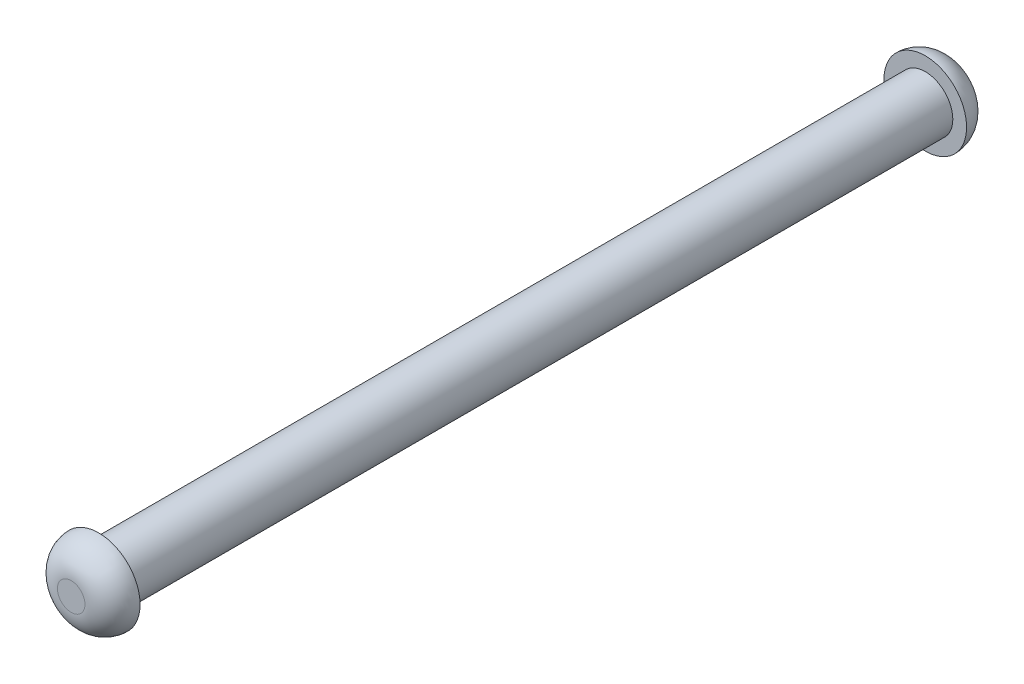
SolidWorks part; units mm, degrees
ref_plane "Ön Düzlem" through (0, 0, 0) normal (0, 0, 1) x (1, 0, 0)
ref_plane "Üst Düzlem" through (0, 0, 0) normal (0, 1, 0) x (1, 0, 0)
ref_plane "Sağ Düzlem" through (0, 0, 0) normal (1, 0, 0) x (0, 0, -1)
sketch "Çizim1" plane through (0, 0, 0) normal (0, 0, 1) x (1, 0, 0)
  circle A0 centre (0, 0) radius 5
extrude "Yükseklik-Ekstrüzyon1" add sketch "Çizim1" along normal blind 150
sketch "Çizim2" plane through (0, 0, 150) normal (0, 0, 1) x (1, 0, 0)
  circle A0 centre (0, 0) radius 7.5
extrude "Yükseklik-Ekstrüzyon2" add sketch "Çizim2" along normal blind 5
fillet "Radyus5" radius 5 1 edges at (7.5, 0, 155)
sketch "Çizim3" plane through (0, 0, 0) normal (0, 0, -1) x (-1, 0, 0)
  circle A0 centre (0, 0) radius 7.5
extrude "Yükseklik-Ekstrüzyon3" add sketch "Çizim3" along normal blind 5
fillet "Radyus6" radius 5 1 edges at (-7.5, 0, -5)
